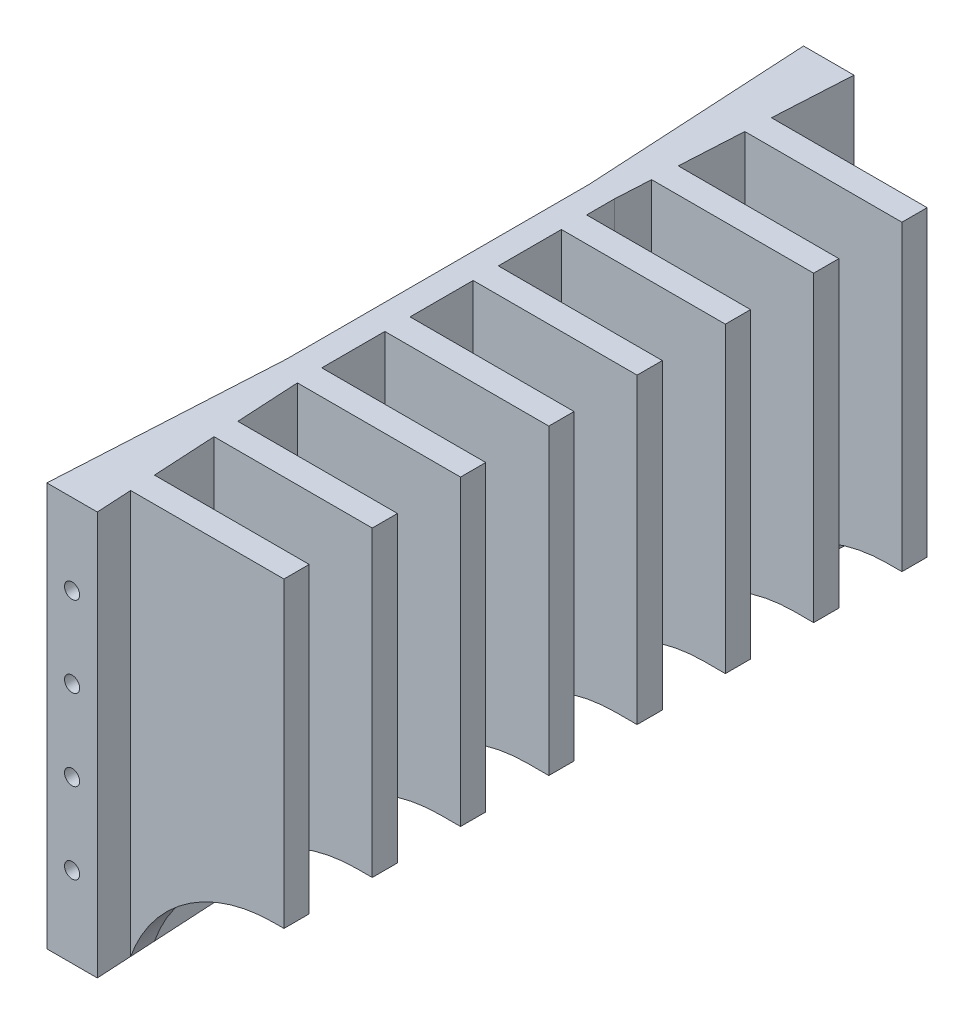
SolidWorks part; units mm, degrees
material "ABS"
ref_plane "Front Plane" through (0, 0, 0) normal (0, 0, 1) x (1, 0, 0)
ref_plane "Top Plane" through (0, 0, 0) normal (0, 1, 0) x (1, 0, 0)
ref_plane "Right Plane" through (0, 0, 0) normal (1, 0, 0) x (0, 0, -1)
sketch "Sketch1" plane through (0, 0, 0) normal (0, 1, 0) x (1, 0, 0)
  line L0 (0, -38.1) -> (0, 38.1)
  line L1 (0, 38.1) -> (-3.175, 95.25)
  line L2 (-3.175, 95.25) -> (9.525, 95.25)
  line L3 (9.525, 95.25) -> (6.35, 38.1)
  line L4 (6.35, 38.1) -> (6.35, -38.1)
  line L5 (6.35, -38.1) -> (9.525, -95.25)
  line L6 (9.525, -95.25) -> (-3.175, -95.25)
  line L7 (-3.175, -95.25) -> (0, -38.1)
  dimension "D1" = 6.35
  dimension "D2" = 190.5
  dimension "D3" = 76.2
  dimension "D4" = 57.15
  dimension "D5" = 12.7
  dimension "D6" = 3.175
extrude "Boss-Extrude1" add sketch "Sketch1" along normal blind 101.6
sketch "Sketch2" plane through (0, 0, 95.25) normal (0, 0, 1) x (1, 0, 0)
  line L0 (-3.175, 0) -> (9.525, 0) construction
  line L2 (-3.175, 101.6) -> (-3.175, 0) construction
  circle A0 centre (3.175, 81.28) radius 1.905
  circle A1 centre (3.175, 60.96) radius 1.905
  circle A2 centre (3.175, 20.32) radius 1.905
  circle A3 centre (3.175, 40.64) radius 1.905
  dimension "D1" = 3.81
  dimension "D2" = 20.32
  dimension "D3" = 20.32
  dimension "D4" = 20.32
  dimension "D5" = 20.32
  dimension "D6" = 6.35
extrude "Cut-Extrude1" cut sketch "Sketch2" against normal blind 4.826
mirror "Mirror1" about plane through (0, 0, 0) normal (0, 0, 1) of "Cut-Extrude1"
sketch "Sketch5" plane through (0, 101.6, 0) normal (0, 1, 0) x (1, 0, 0)
  line L5 (6.35, -38.1) -> (6.35, 38.1) construction
  line L6 (6.35, 69.215) -> (47.625, 69.215)
  line L7 (6.35, 69.215) -> (6.35, 75.565)
  line L8 (6.35, 75.565) -> (47.625, 75.565)
  line L9 (47.625, 69.215) -> (47.625, 75.565)
  line L10 (6.35, 53.34) -> (47.625, 53.34)
  line L11 (6.35, 53.34) -> (6.35, 46.99)
  line L12 (6.35, 46.99) -> (47.625, 46.99)
  line L13 (47.625, 53.34) -> (47.625, 46.99)
  line L14 (6.35, 31.115) -> (47.625, 31.115)
  line L15 (6.35, 31.115) -> (6.35, 24.765)
  line L16 (6.35, 24.765) -> (47.625, 24.765)
  line L17 (47.625, 31.115) -> (47.625, 24.765)
  line L18 (6.35, 8.89) -> (47.625, 8.89)
  line L19 (6.35, 8.89) -> (6.35, 2.54)
  line L20 (6.35, 2.54) -> (47.625, 2.54)
  line L21 (47.625, 8.89) -> (47.625, 2.54)
  line L23 (6.35, -13.335) -> (47.625, -13.335)
  line L24 (6.35, -13.335) -> (6.35, -19.685)
  line L25 (6.35, -19.685) -> (47.625, -19.685)
  line L26 (47.625, -13.335) -> (47.625, -19.685)
  line L27 (6.35, -35.56) -> (47.625, -35.56)
  line L28 (6.35, -35.56) -> (6.35, -41.91)
  line L29 (6.35, -41.91) -> (47.625, -41.91)
  line L30 (47.625, -35.56) -> (47.625, -41.91)
  line L31 (6.35, -57.785) -> (47.625, -57.785)
  line L32 (6.35, -57.785) -> (6.35, -64.135)
  line L33 (6.35, -64.135) -> (47.625, -64.135)
  line L34 (47.625, -57.785) -> (47.625, -64.135)
  line L35 (6.35, -80.01) -> (47.625, -80.01)
  line L36 (6.35, -80.01) -> (6.35, -86.36)
  line L37 (6.35, -86.36) -> (47.625, -86.36)
  line L38 (47.625, -80.01) -> (47.625, -86.36)
  line L39 (-3.175, -95.25) -> (9.525, -95.25) construction
  dimension "D2" = 6.35
  dimension "D4" = 15.875
  dimension "0.475" = 15.875
  dimension "D6" = 15.875
  dimension "D7" = 15.875
  dimension "D8" = 15.875
  dimension "D9" = 15.875
  dimension "D10" = 15.875
  dimension "D11" = 8.89
  dimension "D12" = 50.8
extrude "Boss-Extrude2" add sketch "Sketch5" against normal blind 76.2
fillet "Fillet1" radius 38.1 8 edges at (8.255, 25.4, -72.39) (7.0203, 25.4, -50.165) (6.35, 25.4, -27.94) (6.35, 25.4, -5.715) (6.35, 25.4, 16.51) (7.62, 25.4, 60.96) (8.8547, 25.4, 83.185) (6.4558, 25.4, 40.005)
